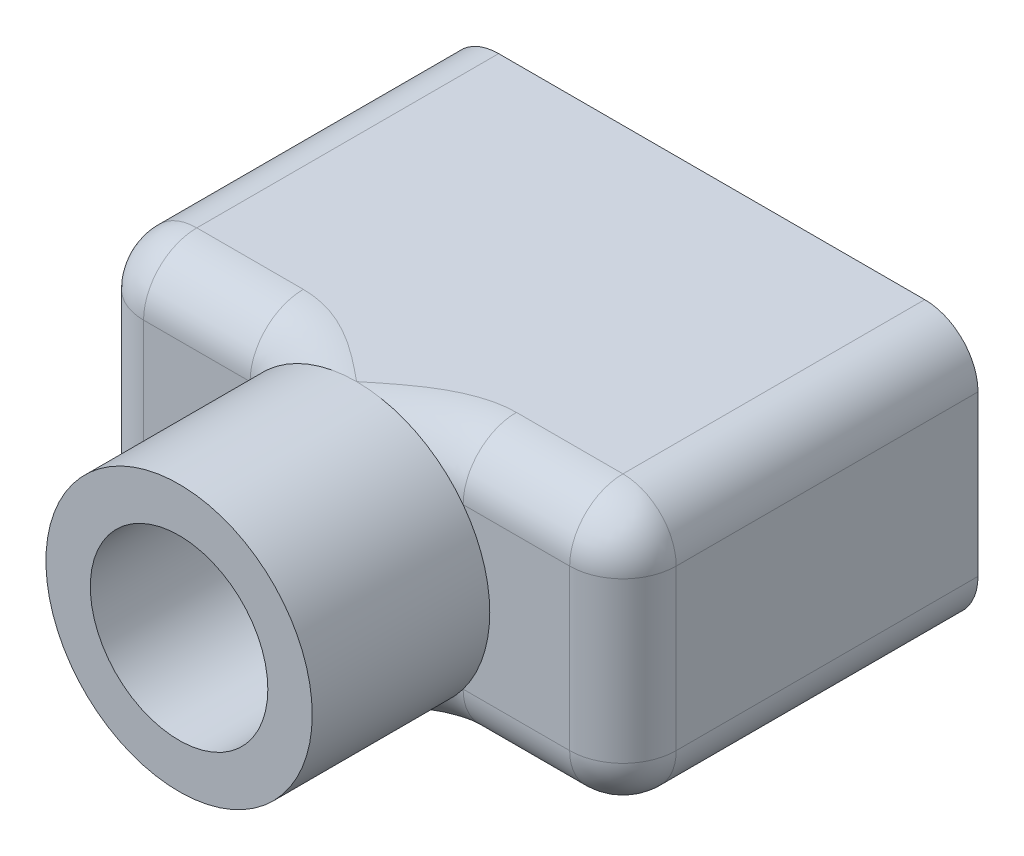
SolidWorks part; units mm, degrees
ref_plane "Front Plane" through (0, 0, 0) normal (0, 0, 1) x (1, 0, 0)
ref_plane "Top Plane" through (0, 0, 0) normal (0, 1, 0) x (1, 0, 0)
ref_plane "Right Plane" through (0, 0, 0) normal (1, 0, 0) x (0, 0, -1)
sketch "Sketch1" plane through (0, 0, 0) normal (0, 0, 1) x (1, 0, 0)
  line L1 (-15, 7.5) -> (15, 7.5)
  line L2 (-15, 7.5) -> (-15, -7.5)
  line L3 (-15, -7.5) -> (15, -7.5)
  line L4 (15, 7.5) -> (15, -7.5)
  line L5 (-15, 7.5) -> (15, -7.5) construction
  line L6 (-15, -7.5) -> (15, 7.5) construction
  point P0 (0, 0)
  dimension "D1" = 7.5
  dimension "D2" = 30
  dimension "D3" = 30
  dimension "D4" = 7.5
extrude "Boss-Extrude1" add sketch "Sketch1" along normal blind 20
sketch "Sketch2" plane through (0, 0, 20) normal (0, 0, 1) x (1, 0, 0)
  circle A0 centre (0, 0) radius 5
  circle A1 centre (0, 0) radius 7.5
  dimension "D1" = 10
  dimension "D2" = 15
extrude "Boss-Extrude2" add sketch "Sketch2" along normal blind 10
fillet "Fillet2" radius 3 10 edges at (-15, -7.5, 10) (15, 7.5, 10) (-15, 7.5, 10) (-15, 0, 20) (7.5, -7.5, 20) (-7.5, -7.5, 20) (15, -7.5, 10) (15, 0, 20) (-7.5, 7.5, 20) (7.5, 7.5, 20)
